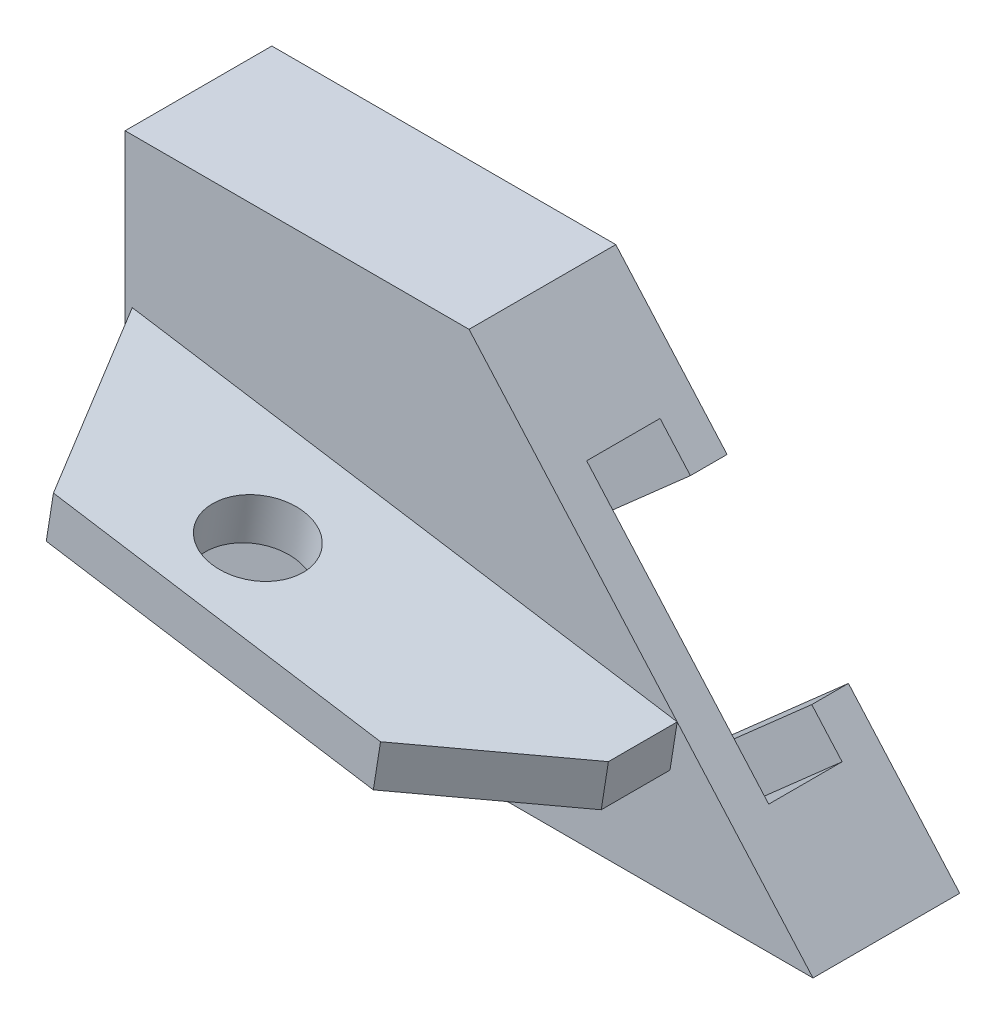
SolidWorks part; units mm, degrees
ref_plane "Front Plane" through (0, 0, 0) normal (0, 0, 1) x (1, 0, 0)
ref_plane "Top Plane" through (0, 0, 0) normal (0, 1, 0) x (1, 0, 0)
ref_plane "Right Plane" through (0, 0, 0) normal (1, 0, 0) x (0, 0, -1)
sketch "Sketch1" plane through (0, 0, 0) normal (0, 0, 1) x (1, 0, 0)
  line L0 (1.5643, 52.3769) -> (120.3913, 33.5565)
  line L1 (0, 0) -> (150, 0)
  line L2 (0, 0) -> (0, 85)
  line L3 (0, 85) -> (75, 85)
  line L5 (120.3913, 33.5565) -> (118.8269, 23.6797)
  line L6 (118.8269, 23.6797) -> (0, 42.5)
  line L7 (0, 42.5) -> (1.5643, 52.3769)
  line L8 (75, 85) -> (150, 0)
  dimension "D1" = 75
  dimension "D2" = 150
  dimension "D3" = 9
  dimension "D4" = 85
  dimension "D5" = 10
extrude "Boss-Extrude1" add sketch "Sketch1" along normal blind 32 contours L8 L3 L2 L7 L0 | L8 L5 L6 L2 L1 region at (52.4608, 62.4018, 0) region at (62.9337, 16.3208, 0)
extrude "Boss-Extrude2" add sketch "Sketch1<4>" along normal blind 72 contours L7 L6 L5 L0 region at (60.1956, 38.0283, 0)
sketch "Sketch1<4>" plane through (0, 0, 0) normal (0, 0, 1) x (1, 0, 0) same geometry as "Sketch1"
sketch "Sketch2" plane through (84.3385, 74.4163, 0) normal (0.7498, 0.6616, 0) x (0, 0, -1)
  line L0 (-8, -22.5643) -> (0, -22.5643)
  line L1 (-24, -12.5643) -> (-8, -12.5643)
  line L2 (-24, -12.5643) -> (-24, -72.5643)
  line L3 (-24, -72.5643) -> (-8, -72.5643)
  line L4 (-8, -12.5643) -> (-8, -22.5643)
  line L5 (-32, 14.1146) -> (0, 14.1146)
  line L6 (-32, 14.1146) -> (-32, -99.2432)
  line L7 (-32, -99.2432) -> (0, -99.2432)
  line L8 (0, 14.1146) -> (0, -99.2432)
  line L9 (-8, -62.5643) -> (0, -62.5643)
  line L10 (-35.5276, -42.5643) -> (-29.3684, -42.5643) construction
  line L11 (0, 14.1146) -> (0, -99.2432) construction
  line L12 (-8, -62.5643) -> (-8, -72.5643)
  point P14 (-16, -72.5643)
  point P15 (-16, -99.2432)
  point P16 (-24, -42.5643)
  point P17 (-32, -42.5643)
  point P20 (-8, -22.5643)
  point P21 (-8, -62.5643)
  point P22 (0, -62.5643)
  point P25 (0, -22.5643)
  dimension "D1" = 40
  dimension "D2" = 60
  dimension "D3" = 16
extrude "Cut-Extrude1" cut sketch "Sketch2" against normal up to next contours L12 L9 L8 L0 L4 L1 L2 L3 region at (112.5, 42.5, 13)
sketch "Sketch3" plane through (6.5666, 41.46, 0) normal (-0.1564, -0.9877, 0) x (0.9877, -0.1564, 0)
  line L0 (-6.6485, 32) -> (16.4455, 72)
  line L1 (113.6597, 72) -> (-6.6485, 72) construction
  line L2 (16.4455, 72) -> (88.6597, 72)
  line L3 (88.6597, 72) -> (113.6597, 47)
  line L4 (113.6597, 72) -> (113.6597, 32) construction
  line L5 (-6.6485, 72) -> (-6.6485, 32) construction
  line L6 (113.6597, 47) -> (113.6597, 32)
  line L7 (113.6597, 32) -> (-6.6485, 32) construction
  circle A0 centre (43.3515, 54) radius 10
  line M4 (113.6597, 32) -> (113.6597, 72)
  line M5 (113.6597, 72) -> (-6.6485, 72)
  line M6 (-6.6485, 72) -> (-6.6485, 32)
  dimension "D4" = 20
  dimension "D1" = 45
  dimension "D2" = 30
  dimension "D3" = 25
  dimension "D5" = 50
  dimension "D6" = 22
extrude "Cut-Extrude2" cut sketch "Sketch3" against normal up to next contours A0 | L3 M5 M4 | L0 M6 M5 region at (7.6032, 41.2958, 58.6667) region at (110.5962, 24.9833, 63.6667) region at (49.3844, 34.6783, 54)
